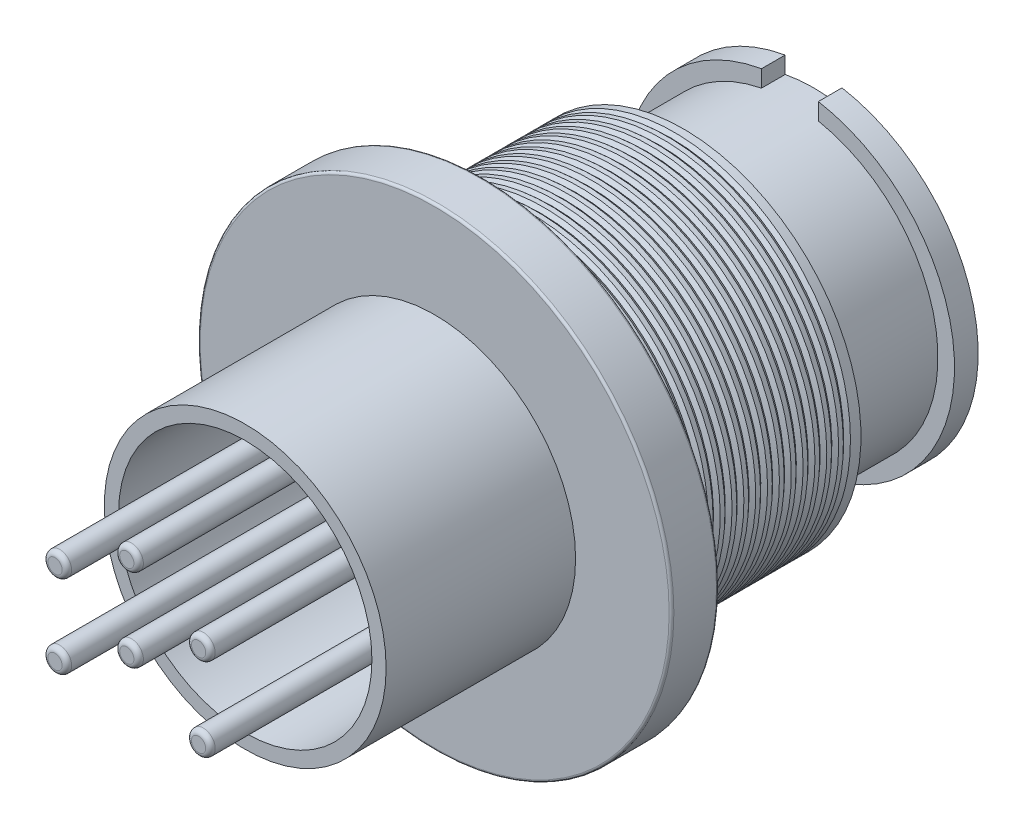
SolidWorks part; units mm, degrees
ref_plane "Спереди" through (0, 0, 0) normal (0, 0, 1) x (1, 0, 0)
ref_plane "Сверху" through (0, 0, 0) normal (0, 1, 0) x (1, 0, 0)
ref_plane "Справа" through (0, 0, 0) normal (1, 0, 0) x (0, 0, -1)
sketch "Эскиз1" plane through (0, 0, 0) normal (0, 0, 1) x (1, 0, 0)
  circle A0 centre (0, 0) radius 10
  dimension "D1" = 20
extrude "Бобышка-Вытянуть1" add sketch "Эскиз1" along normal blind 2
sketch "Эскиз2" plane through (0, 0, 2) normal (0, 0, 1) x (1, 0, 0)
  circle A0 centre (0, 0) radius 5.95
  circle A1 centre (0, 0) radius 5.35
  dimension "D1" = 11.9
  dimension "D2" = 0.6
extrude "Бобышка-Вытянуть2" add sketch "Эскиз2" along normal blind 8
sketch "Эскиз3" plane through (0, 0, 2) normal (0, 0, 1) x (1, 0, 0)
  line L0 (0, 5.35) -> (0, -5.35) construction
  circle A0 centre (0, 0) radius 0.5
  circle A1 centre (0, 0) radius 5.35 construction
  circle A2 centre (0, 0) radius 5.35 construction
  circle A3 centre (0, 3.5) radius 0.5
  circle A4 centre (3.0311, 1.75) radius 0.5
  circle A5 centre (3.0311, -1.75) radius 0.5
  circle A6 centre (0, -3.5) radius 0.5 [skipped]
  circle A7 centre (-3.0311, -1.75) radius 0.5
  circle A8 centre (-3.0311, 1.75) radius 0.5
  dimension "D1" = 1
  dimension "D2" = 3.5
  dimension "D4" = 3.5
  dimension "D5" = 3.0311
  dimension "D3" = 6
extrude "Бобышка-Вытянуть3" add sketch "Эскиз3" along normal blind 13
fillet "Скругление1" radius 0.2 6 edges at (3.5311, -1.75, 15) (3.5311, 1.75, 15) (0.5, 3.5, 15) (0.5, 0, 15) (-2.5311, -1.75, 15) (-2.5311, 1.75, 15)
sketch "Эскиз4" plane through (0, 0, 2) normal (0, 0, 1) x (1, 0, 0)
  circle A2 centre (0, 3.5) radius 0.8
  circle A3 centre (0, 3.5) radius 0.8
  circle A5 centre (-3.0311, 1.75) radius 0.8
  circle A6 centre (-3.0311, 1.75) radius 0.8
  circle A8 centre (0, 0) radius 0.8
  circle A9 centre (0, 0) radius 0.8
  circle A11 centre (3.0311, 1.75) radius 0.8
  circle A12 centre (3.0311, 1.75) radius 0.8
  circle A14 centre (-3.0311, -1.75) radius 0.8
  circle A15 centre (-3.0311, -1.75) radius 0.8
  circle A17 centre (3.0311, -1.75) radius 0.8
  circle A18 centre (3.0311, -1.75) radius 0.8
  dimension "D1" = 0.3
  dimension "D2" = 0.3
  dimension "D3" = 0.3
  dimension "D4" = 0.3
  dimension "D5" = 0.3
  dimension "D6" = 0.3
extrude "Бобышка-Вытянуть4" add sketch "Эскиз4" along normal blind 0.1
fillet "Скругление2" radius 0.1 6 edges at (3.5311, -1.75, 2.1) (3.5311, 1.75, 2.1) (0.5, 0, 2.1) (-2.5311, -1.75, 2.1) (-2.5311, 1.75, 2.1) (0.5, 3.5, 2.1)
sketch "Эскиз5" plane through (0, 0, 0) normal (0, 0, -1) x (-1, 0, 0)
  circle A0 centre (0, 0) radius 7.5
  dimension "D1" = 15
extrude "Бобышка-Вытянуть5" add sketch "Эскиз5" along normal blind 8.5
sketch "Эскиз6" plane through (0, 0, -8.5) normal (0, 0, -1) x (-1, 0, 0)
  circle A0 centre (0, 0) radius 6.25
  dimension "D1" = 12.5
extrude "Бобышка-Вытянуть6" add sketch "Эскиз6" along normal blind 5.5
sketch "Эскиз7" plane through (0, 0, -14) normal (0, 0, -1) x (-1, 0, 0)
  circle A2 centre (0, 0) radius 5.55
  circle A3 centre (0, 0) radius 5.55
  dimension "D1" = 0.7
extrude "Вырез-Вытянуть1" cut sketch "Эскиз7" against normal blind 9
sketch "Эскиз8" plane through (0, 0, -14) normal (0, 0, -1) x (-1, 0, 0)
  circle A0 centre (0, 0) radius 6.25 construction
  circle A1 centre (0, 0) radius 6.25
  circle A2 centre (0, 0) radius 6.95
  dimension "D1" = 0.7
extrude "Бобышка-Вытянуть7" add sketch "Эскиз8" against normal blind 1
sketch "Эскиз9" plane through (0, 0, -5) normal (0, 0, -1) x (-1, 0, 0)
  line L0 (0, 5.55) -> (0, -5.55) construction
  circle A0 centre (0, 0) radius 0.475
  circle A1 centre (0, 0) radius 5.55 construction
  circle A2 centre (0, 0) radius 5.55 construction
  circle A3 centre (0, 3.5) radius 0.475
  circle A4 centre (3.0311, 1.75) radius 0.475
  circle A5 centre (3.0311, -1.75) radius 0.475
  circle A6 centre (0, -3.5) radius 0.475 [skipped]
  circle A7 centre (-3.0311, -1.75) radius 0.475
  circle A8 centre (-3.0311, 1.75) radius 0.475
  dimension "D1" = 0.95
  dimension "D2" = 3.5
  dimension "D4" = 3.5
  dimension "D5" = 3.0311
  dimension "D3" = 6
extrude "Бобышка-Вытянуть8" add sketch "Эскиз9" along normal blind 7.5
fillet "Скругление3" radius 0.3 6 edges at (2.5561, -1.75, -12.5) (-3.5061, -1.75, -12.5) (-3.5061, 1.75, -12.5) (-0.475, 0, -12.5) (2.5561, 1.75, -12.5) (-0.475, 3.5, -12.5)
sketch "Эскиз10" plane through (0, 0, -5) normal (0, 0, -1) x (-1, 0, 0)
  line L0 (0, 5.55) -> (0, -5.55) construction
  line L1 (-0.5, -5.5274) -> (-0.5, -5.0274)
  line L2 (0.5, -5.5274) -> (0.5, -5.0274)
  circle A0 centre (0, 0) radius 5.55 construction
  circle A1 centre (0, 0) radius 5.55 construction
  arc A2 (-0.5, -5.5274) -> (0.5, -5.5274) centre (0, 0) ccw
  arc A3 (-0.5, -5.0274) -> (0.5, -5.0274) centre (0, -5.5274) cw
  dimension "D3" = 0.7071
  dimension "D1" = 0.5
  dimension "D2" = 0.5
extrude "Бобышка-Вытянуть9" add sketch "Эскиз10" along normal blind 8
fillet "Скругление4" radius 0.3 1 edges at (0, -4.8203, -13)
sketch "Эскиз11" plane through (0, 0, -14) normal (0, 0, -1) x (-1, 0, 0)
  line L0 (0, 6.95) -> (0, -6.95) construction
  line L1 (-1.2, 6.8456) -> (-1.2, 6.1337)
  line L2 (-6.25, 0) -> (6.25, 0) construction
  line L3 (1.2, 6.8456) -> (1.2, 6.1337)
  line L4 (1.2, -6.8456) -> (1.2, -6.1337)
  line L5 (-1.2, -6.8456) -> (-1.2, -6.1337)
  circle A0 centre (0, 0) radius 6.25 construction
  arc A1 (-1.2, -6.1337) -> (1.2, -6.1337) centre (0, 0) ccw
  circle A2 centre (0, 0) radius 6.95 construction
  arc A3 (-1.2, -6.8456) -> (1.2, -6.8456) centre (0, 0) ccw
  arc A4 (1.2, 6.8456) -> (-1.2, 6.8456) centre (0, 0) ccw
  arc A5 (1.2, 6.1337) -> (-1.2, 6.1337) centre (0, 0) ccw
  point P7 (-1.2, 6.8456)
  dimension "D1" = 1.2
extrude "Вырез-Вытянуть2" cut sketch "Эскиз11" against normal blind 2
sketch "Эскиз12" plane through (0, 0, 0) normal (0, 0, -1) x (-1, 0, 0)
  circle A0 centre (0, 0) radius 7.5 construction
  circle A1 centre (0, 0) radius 7.5
curve "Спираль1" pitch 0.5 height 8.375 radius 7.5 left hand yes centre (0, 0, 0) axis (0, 0, -1) start towards (0.7071, 0.7071, 0)
sketch "Эскиз13" plane through (0, 0, 0) normal (0, 1, 0) x (1, 0, 0)
  line L0 (-7.5, 8.3064) -> (-7.3508, 8.1716)
  line L1 (-7.5, 8.5) -> (-7.5, 0) construction
  line L2 (-7.3508, 8.1716) -> (-7.5, 8.0064)
  line L3 (-7.5, 8.0064) -> (-7.5, 8.3064)
  spline S0 degree 3 poles (5.3033, 0) (4.6136, 0.0103) (2.9428, 0.0313) (0.0005, 0.0625) (-2.945, 0.0938) (-5.4413, 0.125) (-7.1095, 0.1563) (-7.6953, 0.1875) (-7.1095, 0.2188) (-5.4414, 0.25) (-2.9448, 0.2813) (0, 0.3125) (2.9448, 0.3438) (5.4414, 0.375) (7.1095, 0.4063) (7.6953, 0.4375) (7.1095, 0.4688) (5.4414, 0.5) (2.9448, 0.5313) (0, 0.5625) (-2.9448, 0.5938) (-5.4414, 0.625) (-7.1095, 0.6563) (-7.6953, 0.6875) (-7.1095, 0.7188) (-5.4414, 0.75) (-2.9448, 0.7813) (0, 0.8125) (2.9448, 0.8438) (5.4414, 0.875) (7.1095, 0.9063) (7.6953, 0.9375) (7.1095, 0.9688) (5.4414, 1) (2.9448, 1.0312) (0, 1.0625) (-2.9448, 1.0938) (-5.4414, 1.125) (-7.1095, 1.1563) (-7.6953, 1.1875) (-7.1095, 1.2188) (-5.4414, 1.25) (-2.9448, 1.2813) (0, 1.3125) (2.9448, 1.3438) (5.4414, 1.375) (7.1095, 1.4063) (7.6953, 1.4375) (7.1095, 1.4688) (5.4414, 1.5) (2.9448, 1.5313) (0, 1.5625) (-2.9448, 1.5938) (-5.4414, 1.625) (-7.1095, 1.6563) (-7.6953, 1.6875) (-7.1095, 1.7188) (-5.4414, 1.75) (-2.9448, 1.7813) (0, 1.8125) (2.9448, 1.8438) (5.4414, 1.875) (7.1095, 1.9063) (7.6953, 1.9375) (7.1095, 1.9688) (5.4414, 2) (2.9448, 2.0313) (0, 2.0625) (-2.9448, 2.0938) (-5.4414, 2.125) (-7.1095, 2.1563) (-7.6953, 2.1875) (-7.1095, 2.2188) (-5.4414, 2.25) (-2.9448, 2.2813) (0, 2.3125) (2.9448, 2.3438) (5.4414, 2.375) (7.1095, 2.4063) (7.6953, 2.4375) (7.1095, 2.4688) (5.4414, 2.5) (2.9448, 2.5313) (0, 2.5625) (-2.9448, 2.5938) (-5.4414, 2.625) (-7.1095, 2.6563) (-7.6953, 2.6875) (-7.1095, 2.7188) (-5.4414, 2.75) (-2.9448, 2.7813) (0, 2.8125) (2.9448, 2.8438) (5.4414, 2.875) (7.1095, 2.9063) (7.6953, 2.9375) (7.1095, 2.9688) (5.4414, 3) (2.9448, 3.0313) (0, 3.0625) (-2.9448, 3.0938) (-5.4414, 3.125) (-7.1095, 3.1563) (-7.6953, 3.1875) (-7.1095, 3.2188) (-5.4414, 3.25) (-2.9448, 3.2813) (0, 3.3125) (2.9448, 3.3438) (5.4414, 3.375) (7.1095, 3.4063) (7.6953, 3.4375) (7.1095, 3.4688) (5.4414, 3.5) (2.9448, 3.5313) (0, 3.5625) (-2.9448, 3.5938) (-5.4414, 3.625) (-7.1095, 3.6563) (-7.6953, 3.6875) (-7.1095, 3.7188) (-5.4414, 3.75) (-2.9448, 3.7813) (0, 3.8125) (2.9448, 3.8438) (5.4414, 3.875) (7.1095, 3.9063) (7.6953, 3.9375) (7.1095, 3.9688) (5.4414, 4) (2.9448, 4.0313) (0, 4.0625) (-2.9448, 4.0938) (-5.4414, 4.125) (-7.1095, 4.1563) (-7.6953, 4.1875) (-7.1095, 4.2188) (-5.4414, 4.25) (-2.9448, 4.2813) (0, 4.3125) (2.9448, 4.3438) (5.4414, 4.375) (7.1095, 4.4063) (7.6953, 4.4375) (7.1095, 4.4688) (5.4414, 4.5) (2.9448, 4.5313) (0, 4.5625) (-2.9448, 4.5938) (-5.4414, 4.625) (-7.1095, 4.6563) (-7.6953, 4.6875) (-7.1095, 4.7188) (-5.4414, 4.75) (-2.9448, 4.7813) (0, 4.8125) (2.9448, 4.8438) (5.4414, 4.875) (7.1095, 4.9063) (7.6953, 4.9375) (7.1095, 4.9688) (5.4414, 5) (2.9448, 5.0313) (0, 5.0625) (-2.9448, 5.0938) (-5.4414, 5.125) (-7.1095, 5.1563) (-7.6953, 5.1875) (-7.1095, 5.2188) (-5.4414, 5.25) (-2.9448, 5.2813) (0, 5.3125) (2.9448, 5.3438) (5.4414, 5.375) (7.1095, 5.4063) (7.6953, 5.4375) (7.1095, 5.4688) (5.4414, 5.5) (2.9448, 5.5313) (0, 5.5625) (-2.9448, 5.5938) (-5.4414, 5.625) (-7.1095, 5.6563) (-7.6953, 5.6875) (-7.1095, 5.7188) (-5.4414, 5.75) (-2.9448, 5.7813) (0, 5.8125) (2.9448, 5.8438) (5.4414, 5.875) (7.1095, 5.9063) (7.6953, 5.9375) (7.1095, 5.9688) (5.4414, 6) (2.9448, 6.0313) (0, 6.0625) (-2.9448, 6.0938) (-5.4414, 6.125) (-7.1095, 6.1563) (-7.6953, 6.1875) (-7.1095, 6.2188) (-5.4414, 6.25) (-2.9448, 6.2813) (0, 6.3125) (2.9448, 6.3438) (5.4414, 6.375) (7.1095, 6.4063) (7.6953, 6.4375) (7.1095, 6.4688) (5.4414, 6.5) (2.9448, 6.5313) (0, 6.5625) (-2.9448, 6.5938) (-5.4414, 6.625) (-7.1095, 6.6563) (-7.6953, 6.6875) (-7.1095, 6.7188) (-5.4414, 6.75) (-2.9448, 6.7813) (0, 6.8125) (2.9448, 6.8438) (5.4414, 6.875) (7.1095, 6.9063) (7.6953, 6.9375) (7.1095, 6.9688) (5.4414, 7) (2.9448, 7.0313) (0, 7.0625) (-2.9448, 7.0938) (-5.4414, 7.125) (-7.1095, 7.1563) (-7.6953, 7.1875) (-7.1095, 7.2188) (-5.4414, 7.25) (-2.9448, 7.2813) (0, 7.3125) (2.9448, 7.3438) (5.4414, 7.375) (7.1095, 7.4063) (7.6953, 7.4375) (7.1095, 7.4688) (5.4414, 7.5) (2.9448, 7.5313) (0, 7.5625) (-2.9448, 7.5938) (-5.4414, 7.625) (-7.1095, 7.6563) (-7.6953, 7.6875) (-7.1095, 7.7188) (-5.4414, 7.75) (-2.9448, 7.7813) (0, 7.8125) (2.9448, 7.8437) (5.4414, 7.875) (7.1095, 7.9062) (7.6953, 7.9375) (7.1095, 7.9687) (5.4414, 8) (2.9448, 8.0312) (0, 8.0625) (-2.9448, 8.0937) (-5.4414, 8.125) (-7.1095, 8.1562) (-7.6953, 8.1875) (-7.1095, 8.2187) (-5.4413, 8.25) (-2.945, 8.2812) (0.0005, 8.3125) (2.9428, 8.3437) (4.6136, 8.3647) (5.3033, 8.375) knots 0 0 0 0 0.003731 0.007463 0.011194 0.014925 0.018657 0.022388 0.026119 0.029851 0.033582 0.037313 0.041045 0.044776 0.048507 0.052239 0.05597 0.059701 0.063433 0.067164 0.070896 0.074627 0.078358 0.08209 0.085821 0.089552 0.093284 0.097015 0.100746 0.104478 0.108209 0.11194 0.115672 0.119403 0.123134 0.126866 0.130597 0.134328 0.13806 0.141791 0.145522 0.149254 0.152985 0.156716 0.160448 0.164179 0.16791 0.171642 0.175373 0.179104 0.182836 0.186567 0.190299 0.19403 0.197761 0.201493 0.205224 0.208955 0.212687 0.216418 0.220149 0.223881 0.227612 0.231343 0.235075 0.238806 0.242537 0.246269 0.25 0.253731 0.257463 0.261194 0.264925 0.268657 0.272388 0.276119 0.279851 0.283582 0.287313 0.291045 0.294776 0.298507 0.302239 0.30597 0.309701 0.313433 0.317164 0.320896 0.324627 0.328358 0.33209 0.335821 0.339552 0.343284 0.347015 0.350746 0.354478 0.358209 0.36194 0.365672 0.369403 0.373134 0.376866 0.380597 0.384328 0.38806 0.391791 0.395522 0.399254 0.402985 0.406716 0.410448 0.414179 0.41791 0.421642 0.425373 0.429104 0.432836 0.436567 0.440299 0.44403 0.447761 0.451493 0.455224 0.458955 0.462687 0.466418 0.470149 0.473881 0.477612 0.481343 0.485075 0.488806 0.492537 0.496269 0.5 0.503731 0.507463 0.511194 0.514925 0.518657 0.522388 0.526119 0.529851 0.533582 0.537313 0.541045 0.544776 0.548507 0.552239 0.55597 0.559701 0.563433 0.567164 0.570896 0.574627 0.578358 0.58209 0.585821 0.589552 0.593284 0.597015 0.600746 0.604478 0.608209 0.61194 0.615672 0.619403 0.623134 0.626866 0.630597 0.634328 0.63806 0.641791 0.645522 0.649254 0.652985 0.656716 0.660448 0.664179 0.66791 0.671642 0.675373 0.679104 0.682836 0.686567 0.690299 0.69403 0.697761 0.701493 0.705224 0.708955 0.712687 0.716418 0.720149 0.723881 0.727612 0.731343 0.735075 0.738806 0.742537 0.746269 0.75 0.753731 0.757463 0.761194 0.764925 0.768657 0.772388 0.776119 0.779851 0.783582 0.787313 0.791045 0.794776 0.798507 0.802239 0.80597 0.809701 0.813433 0.817164 0.820896 0.824627 0.828358 0.83209 0.835821 0.839552 0.843284 0.847015 0.850746 0.854478 0.858209 0.86194 0.865672 0.869403 0.873134 0.876866 0.880597 0.884328 0.88806 0.891791 0.895522 0.899254 0.902985 0.906716 0.910448 0.914179 0.91791 0.921642 0.925373 0.929104 0.932836 0.936567 0.940299 0.94403 0.947761 0.951493 0.955224 0.958955 0.962687 0.966418 0.970149 0.973881 0.977612 0.981343 0.985075 0.988806 0.992537 0.996269 1 1 1 1 construction
  dimension "D1" = 0.3
  dimension "D2" = 0.1936
sweep "Вырез-По траектории1" cut profiles "Эскиз13" path "Спираль1"
ref_plane "Плоскость1" through (0, 0, -20) normal (0, 0, 1) x (1, 0, 0)
sketch "Эскиз14" plane through (0, 0, -20) normal (0, 0, 1) x (1, 0, 0)
  line L0 (10, 0) -> (-10, 0) construction
  line L1 (-7.2284, 2) -> (-7.2284, -2)
  circle A0 centre (0, 0) radius 10 construction
  circle A1 centre (0, 0) radius 7.5 construction
  arc A2 (-7.2284, 2) -> (-7.2284, -2) centre (-3.9363, 0) ccw
  dimension "D2" = 3.852
  dimension "D1" = 4
extrude "Вырез-Вытянуть3" cut sketch "Эскиз14" along normal up to surface (20 mm away) up to face at (0, 0, 0)
fillet "Скругление5" radius 0.1 2 edges at (10, 0, 0) (10, 0, 2)
